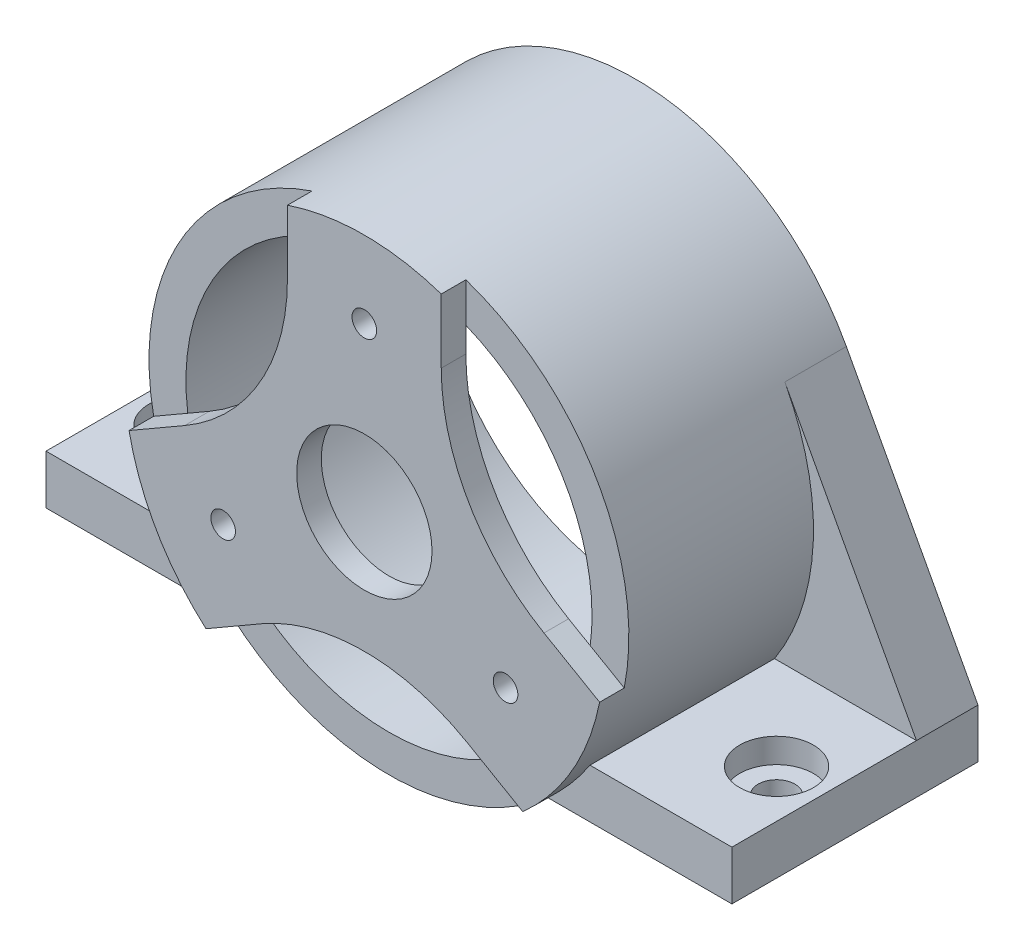
SolidWorks part; units mm, degrees
ref_plane "前视基准面" through (0, 0, 0) normal (0, 0, 1) x (1, 0, 0)
ref_plane "上视基准面" through (0, 0, 0) normal (0, 1, 0) x (1, 0, 0)
ref_plane "右视基准面" through (0, 0, 0) normal (1, 0, 0) x (0, 0, -1)
sketch "草图1" plane through (0, 0, 0) normal (0, 0, 1) x (1, 0, 0)
  line L0 (0, 0) -> (0, 16.5)
  line L1 (0, -16.5) -> (50.4081, -16.5)
  line L2 (50.4081, -16.5) -> (-45.4134, -16.5)
  line L3 (0, 13.25) -> (-6.25, 13.25)
  line L4 (0, 13.25) -> (6.25, 13.25)
  line L5 (11.4748, -6.625) -> (14.5998, -1.2123)
  line L6 (11.4748, -6.625) -> (8.3498, -12.0377)
  line L7 (-11.4748, -6.625) -> (-8.3498, -12.0377)
  line L8 (-11.4748, -6.625) -> (-14.5998, -1.2123)
  line L9 (0, 13.25) -> (-25.1186, 13.25)
  line L10 (-25.1186, 13.25) -> (19.2974, 13.25)
  line L11 (11.4748, -6.625) -> (24.0341, 15.1283)
  line L12 (24.0341, 15.1283) -> (1.8261, -23.337)
  line L13 (-11.4748, -6.625) -> (1.0845, -28.3783)
  line L14 (1.0845, -28.3783) -> (-21.1235, 10.087)
  line L15 (-11.4748, -6.625) -> (-22.9497, 13.25)
  line L16 (-6.25, 13.25) -> (-6.25, 18.4713)
  line L17 (6.25, 13.25) -> (6.25, 18.4713)
  line L18 (14.5998, -1.2123) -> (19.1216, -3.823)
  line L19 (8.3498, -12.0377) -> (12.8716, -14.6483)
  line L20 (-8.3498, -12.0377) -> (-12.8716, -14.6483)
  line L21 (-14.5998, -1.2123) -> (-19.1216, -3.823)
  circle A0 centre (0, 0) radius 16.5
  circle A1 centre (0, 0) radius 5.5
  circle A2 centre (0, 0) radius 13.25
  circle A6 centre (0, 0) radius 19.5
  circle A7 centre (0, 13.25) radius 1
  circle A8 centre (0, 13.25) radius 6.25
  circle A9 centre (11.4748, -6.625) radius 6.25
  circle A10 centre (11.4748, -6.625) radius 1
  circle A11 centre (-11.4748, -6.625) radius 6.25
  circle A12 centre (-11.4748, -6.625) radius 1
  circle A13 centre (-22.9497, 13.25) radius 16.6997
  circle A14 centre (22.9497, 13.25) radius 16.6997
  circle A15 centre (0, -26.5) radius 16.6997
  point P14 (0, 0)
  point P28 (0, 0)
  point P37 (0, 0)
  point P44 (0, 0)
  point P55 (0, 0)
  dimension "D1" = 33
  dimension "D2" = 11
  dimension "D3" = 26.5
  dimension "D4" = 2
  dimension "D6" = 39
  dimension "D5" = 3
  dimension "D7" = 3
  dimension "D8" = 3
  dimension "D9" = 3
extrude "凸台-拉伸1" add sketch "草图1" along normal blind 2 contours A8 A6 L16 A0 | A8 A0 L17 A6 | A0 A8 | A0 A8 L10 A7 L0 | L10 A8 A0 L0 A7 | A2 A8 L0 A7 | L0 A8 A2 A7 | L10 A8 A2 A7 | A8 A0 L16 | A8 L17 A0 | A2 A8 L10 A7 | A11 A0 L21 A6 | A11 L21 A0 | A12 L15 A11 A0 L14 | A12 A2 A11 | A12 A2 A11 L15 | A0 A11 | A12 L14 A11 A2 | A11 A6 L20 A0 | A11 A0 L20 | A13 A11 A2 | A15 A2 A11 | A9 A6 L18 A0 | A9 A0 L18 | A14 A2 A9 | A15 A2 A9 A14 A8 A1 A13 A11 | A10 A2 A9 | A10 L12 A9 A2 | A10 L12 A9 A0 | A9 A0 L19 A6 | A0 A9 | A10 A2 A9 L12 | A15 A9 A2 | A9 L19 A0 | A14 A8 A2 | A13 A2 A8 region at (4.0804, 8.0608, 0) region at (-2.4856, 10.2791, 0) region at (2.4856, 10.2791, 0) region at (-4.6771, 12.804, 0) region at (-6.2195, 12.0943, 0) region at (6.2195, 12.0943, 0) region at (4.6771, 12.804, 0) region at (-2.9697, 14.7426, 0) region at (-6.135, 14.8262, 0) region at (6.135, 14.8262, 0) region at (2.9697, 14.7426, 0) region at (-13.5837, -0.6609, 0) region at (-4.8565, 17.8562, 0) region at (0, 17.5151, 0) region at (13.5837, -0.6609, 0) region at (4.8565, 17.8562, 0) region at (-8.902, -5.1395, 0) region at (-13.4272, -2.3515, 0) region at (-15.9074, -2.1, 0) region at (-12.7674, -7.3713, 0) region at (13.4272, -2.3515, 0) region at (8.902, -5.1395, 0) region at (12.7674, -7.3713, 0) region at (15.9074, -2.1, 0) region at (-17.8921, -4.7222, 0) region at (-15.1685, -8.7576, 0) region at (7.3642, -11.4334, 0) region at (8.7501, -10.4525, 0) region at (17.8921, -4.7222, 0) region at (15.1685, -8.7576, 0) region at (-8.7501, -10.4525, 0) region at (-7.3642, -11.4334, 0) region at (-9.7723, -12.7262, 0) region at (-13.0356, -13.1339, 0) region at (9.7723, -12.7262, 0) region at (13.0356, -13.1339, 0)
extrude "凸台-拉伸2" add sketch "草图1<3>" against normal blind 20 contours A0 A8 | A8 A6 L16 A0 | A0 A13 A6 L10 | A13 A0 L16 A6 | A14 A6 L17 A0 | A6 A14 A0 L10 | L12 A6 L10 A0 | L10 A6 L15 A0 | A6 A13 A0 L15 | A13 A6 L21 A0 | A11 A0 L21 A6 | A0 A11 | A11 A6 L20 A0 | A9 A0 L19 A6 | A0 A9 | A9 A6 L18 A0 | A0 A14 A6 L12 | A14 A0 L18 A6 | A8 A0 L17 A6 | A6 A15 A0 L12 L2 | A15 A6 L19 A0 | A0 A15 A6 L2 L14 | A15 A0 L20 A6 region at (-15.2379, 8.7976, 0) region at (-9.6703, 15.2673, 0) region at (-6.4886, 17.2192, 0) region at (-4.8565, 17.8562, 0) region at (0, 17.5151, 0) region at (9.6703, 15.2673, 0) region at (15.2379, 8.7976, 0) region at (4.8565, 17.8562, 0) region at (6.4886, 17.2192, 0) region at (-18.057, 0.741, 0) region at (18.057, 0.741, 0) region at (-17.8921, -4.7222, 0) region at (-18.1566, -2.9903, 0) region at (-15.1685, -8.7576, 0) region at (18.1566, -2.9903, 0) region at (17.8921, -4.7222, 0) region at (15.1685, -8.7576, 0) region at (-13.0356, -13.1339, 0) region at (13.0356, -13.1339, 0) region at (-11.668, -14.229, 0) region at (9.1987, -15.2174, 0) region at (11.668, -14.229, 0) region at (-9.1987, -15.2174, 0)
sketch "草图1<3>" plane through (0, 0, 0) normal (0, 0, 1) x (1, 0, 0) same geometry as "草图1"
extrude "凸台-拉伸3" add sketch "草图1<4>" against normal blind 20 contours A0 L1 L12 | L12 A6 L2 | L13 A6 L12 L1 L2 | A0 L14 L2 | L2 A6 L13 region at (4.6278, -16.106, 0) region at (-4.6278, -16.106, 0) region at (0, -17.8475, 0) region at (6.9283, -17.4292, 0) region at (-6.9283, -17.4292, 0)
sketch "草图1<4>" plane through (0, 0, 0) normal (0, 0, 1) x (1, 0, 0) same geometry as "草图1"
ref_plane "基准面4" through (0, -14.6483, 0) normal (0, 1, 0) x (1, 0, 0)
sketch "草图4" plane through (0, 0, 0) normal (0, 0, -1) x (-1, 0, 0)
  line L0 (0, 0) -> (0, -16.5)
  line L1 (0, -16.5) -> (36.7873, -16.5)
  circle A0 centre (0, 0) radius 16.5 construction
sketch "草图6" plane through (0, -14.6483, 0) normal (0, 1, 0) x (1, 0, 0)
  line L0 (-12.8716, -2) -> (-27.8716, -2)
  line L1 (-27.8716, -2) -> (-27.8716, 20)
  line L2 (-27.8716, 20) -> (27.8716, 20)
  line L3 (27.8716, 20) -> (27.8716, -2)
  line L4 (27.8716, -2) -> (12.8716, -2)
  line L5 (-12.8716, -2) -> (-12.8716, 20)
  line L6 (12.8716, -2) -> (12.8716, 20)
  line L7 (-12.8716, -2) -> (-12.8716, 0)
  line L8 (-12.8716, 0) -> (-36.9191, 0)
  line L9 (-27.8716, 0) -> (27.8716, 0)
  point P14 (-27.8716, 0)
  dimension "D1" = 15
  dimension "D2" = 22
  dimension "D3" = 15
extrude "凸台-拉伸9" add sketch "草图6" along normal blind 4 contours L6 L9 L3 L2 | L8 L5 L2 L1 region at (-20.3716, -14.6483, -10) region at (20.3716, -14.6483, -10)
sketch "草图8" plane through (0, 0, -20) normal (0, 0, -1) x (-1, 0, 0)
  line L0 (-27.8716, -10.6483) -> (-17.1726, 9.2387)
  line L1 (-27.8716, -10.6483) -> (-16.336, -10.6483)
  line L2 (16.336, -10.6483) -> (27.8716, -10.6483)
  line L3 (27.8716, -10.6483) -> (17.1726, 9.2387)
  line L4 (17.1726, 9.2387) -> (34.6888, 4.2849)
  arc A0 (16.336, -10.6483) -> (-16.336, -10.6483) centre (0, 0) ccw construction
  arc A1 (16.336, -10.6483) -> (-16.336, -10.6483) centre (0, 0) ccw
  line M5 (27.8716, -10.6483) -> (16.336, -10.6483)
  arc M6 (16.336, -10.6483) -> (-16.336, -10.6483) centre (0, 0) ccw
  line M7 (-16.336, -10.6483) -> (-27.8716, -10.6483)
extrude "凸台-拉伸10" add sketch "草图8" against normal blind 5 contours L0 M7 M6 region at (21.6907, -5.5618, -20)
extrude "凸台-拉伸11" add sketch "草图8<3>" against normal blind 5 contours L3 M5 M6 region at (-21.6907, -5.5618, -20)
sketch "草图8<3>" plane through (0, 0, -20) normal (0, 0, -1) x (-1, 0, 0) same geometry as "草图8"
sketch "草图9" plane through (0, -10.6483, 0) normal (0, 1, 0) x (1, 0, 0)
  line L0 (27.8716, 0) -> (27.8716, 15)
  line L1 (27.8716, 7.5) -> (-27.8716, 7.5)
  line L3 (-27.8716, 0) -> (-27.8716, 15) construction
  line L4 (0, 7.5) -> (24, 7.5)
  line L5 (0, -12.1) -> (0, 12.1) construction
  circle A2 centre (24, 7.5) radius 1.5
  circle A3 centre (-24, 7.5) radius 1.5
  dimension "D1" = 24
  dimension "D2" = 3
extrude "切除-拉伸3" cut sketch "草图9" against normal blind 10 contours A3 L1 | A3 L1 | L1 A2 | L1 A2 region at (24, -10.6483, -6.8634) region at (24, -10.6483, -8.1366) region at (-24, -10.6483, -6.8634) region at (-24, -10.6483, -8.1366)
sketch "草图11" plane through (0, -10.6483, 0) normal (0, 1, 0) x (1, 0, 0)
  circle A0 centre (-24, 7.5) radius 3
  circle A1 centre (24, 7.5) radius 3
  dimension "D1" = 6
  dimension "D2" = 6
extrude "切除-拉伸4" cut sketch "草图11" against normal blind 2
